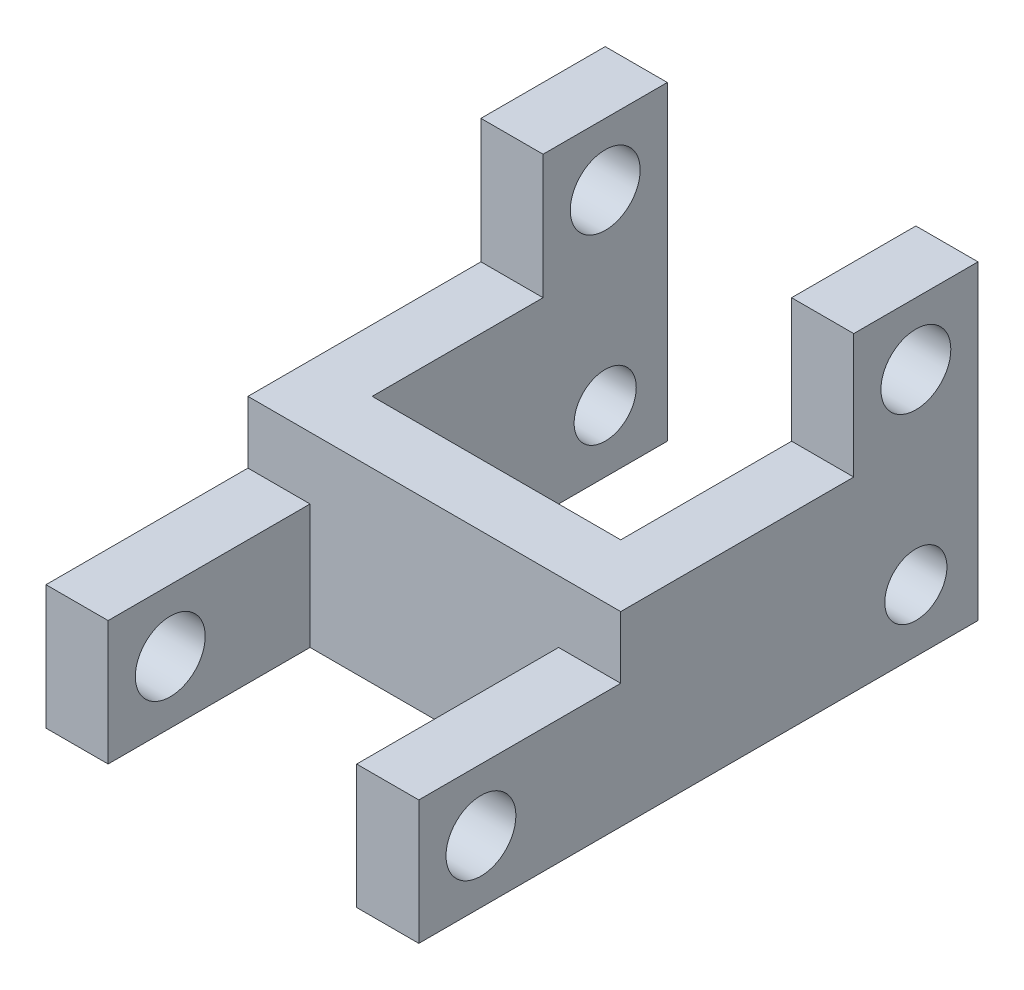
SolidWorks part; units mm, degrees
ref_plane "Front Plane" through (0, 0, 0) normal (0, 0, 1) x (1, 0, 0)
ref_plane "Top Plane" through (0, 0, 0) normal (0, 1, 0) x (1, 0, 0)
ref_plane "Right Plane" through (0, 0, 0) normal (1, 0, 0) x (0, 0, -1)
sketch "Sketch1" plane through (0, 0, 0) normal (1, 0, 0) x (0, 0, -1)
  line L0 (0, 0) -> (64.407, 138.1213) construction
  line L1 (-25.4, -25.4) -> (203.2, -25.4)
  line L2 (-25.4, -25.4) -> (-25.4, 50.8)
  line L3 (-25.4, 50.8) -> (152.4, 50.8)
  line L4 (82.55, 50.8) -> (57.15, 50.8)
  line L5 (82.55, 50.8) -> (82.55, -25.4)
  line L6 (203.2, -25.4) -> (203.2, 101.6)
  line L7 (203.2, 101.6) -> (152.4, 101.6)
  line L8 (152.4, 50.8) -> (152.4, 101.6)
  line L9 (82.55, -25.4) -> (57.15, -25.4)
  line L10 (57.15, 50.8) -> (57.15, -25.4)
  line L11 (64.407, 138.1213) -> (203.7687, 147.8385) construction
  line L12 (203.7687, 147.8385) -> (177.8, 76.2) construction
  line L13 (0, 0) -> (0, 152.4) construction
  line L14 (0, 152.4) -> (139.3097, 141.9642) construction
  line L15 (139.3097, 141.9642) -> (177.8, 76.2) construction
  line L16 (23.0202, -10.7345) -> (87.4272, 127.3868) construction
  line L17 (-23.0202, 10.7345) -> (41.3868, 148.8558) construction
  circle A0 centre (0, 0) radius 14.2875
  circle A1 centre (177.8, 76.2) radius 14.2875
  circle A2 centre (177.8, 0) radius 12.7
  dimension "D1" = 28.575
  dimension "D10" = 25.4
  dimension "D11" = 177.8
  dimension "D2" = 76.2
  dimension "D3" = 25.4
  dimension "D4" = 57.15
  dimension "D5" = 25.4
  dimension "D6" = 25.4
  dimension "D7" = 25.4
  dimension "D8" = 50.8
  dimension "D9" = 101.6
  dimension "D12" = 25.4
  dimension "D13" = 152.4
  dimension "D14" = 139.7
  dimension "D15" = 76.2
  dimension "D16" = 65
  dimension "D17" = 25.4
  dimension "D18" = 25.4
extrude "Boss-Extrude1" add sketch "Sketch1" along normal blind 25.4 contours L10 L3 L2 L1 A0 | L3 L10 L1 L5 | L8 L3 L5 L1 L6 L7 A2 A1 region at (0, 14.1418, -17.6772) region at (0, 12.7, -69.85) region at (0, 24.8947, -147.5836)
extrude "Boss-Extrude2" add sketch "Sketch1<3>" against normal blind 101.6 contours L3 L10 L1 L5 region at (0, 12.7, -69.85)
sketch "Sketch1<3>" plane through (0, 0, 0) normal (1, 0, 0) x (0, 0, -1) same geometry as "Sketch1"
extrude "Boss-Extrude4" add sketch "Sketch1<4>" against normal blind 25.4 from vertex contours L3 L10 L1 L5 | L8 L3 L5 L1 L6 L7 A2 A1 | L10 L3 L2 L1 A0 region at (0, 14.1418, -17.6772) region at (0, 12.7, -69.85) region at (0, 24.8947, -147.5836) starting at point (-101.6, 50.8, -82.55)
sketch "Sketch1<4>" plane through (0, 0, 0) normal (1, 0, 0) x (0, 0, -1) same geometry as "Sketch1"
sketch "Sketch2" plane through (25.4, 0, 0) normal (1, 0, 0) x (0, 0, -1)
  line L1 (-25.4, 50.8) -> (57.15, 50.8)
  line L2 (-25.4, 50.8) -> (-25.4, 25.4)
  line L3 (-25.4, 25.4) -> (57.15, 25.4)
  line L4 (57.15, 50.8) -> (57.15, 25.4)
  dimension "D2" = 25.4
extrude "Cut-Extrude1" cut sketch "Sketch2" against normal through all
